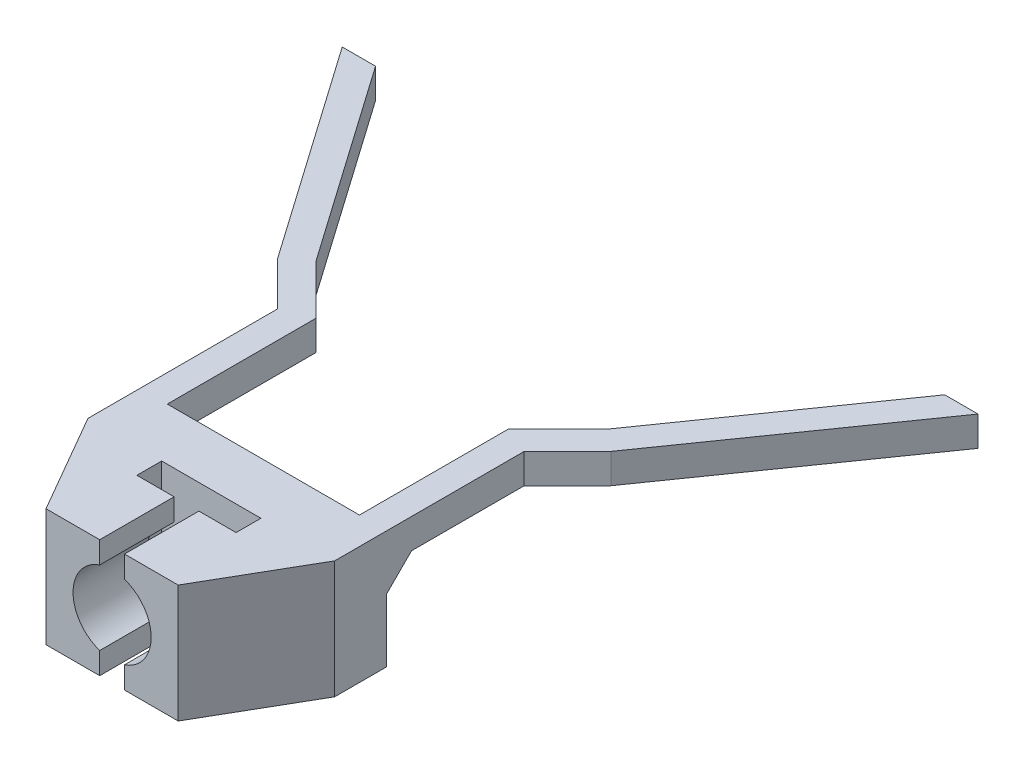
SolidWorks part; units mm, degrees
ref_plane "Front" through (0, 0, 0) normal (0, 0, 1) x (1, 0, 0)
ref_plane "Top" through (0, 0, 0) normal (0, 1, 0) x (1, 0, 0)
ref_plane "Right" through (0, 0, 0) normal (1, 0, 0) x (0, 0, -1)
ref_axis "X" through (-80.9, 0, 0) along (1, 0, 0)
ref_axis "Y" through (0, -50, 0) along (0, 1, 0)
ref_axis "Z" through (0, 0, -80.9) along (0, 0, 1)
sketch "Sketch1" plane through (0, 0, 0) normal (0, 1, 0) x (1, 0, 0)
  line L0 (-7.75, 0) -> (0, 0)
  line L1 (-7.75, 0) -> (-7.75, 12)
  line L2 (-11.75, 16) -> (-22.9533, 32)
  line L3 (-22.9533, 32) -> (-25.639, 32)
  line L4 (-7.75, 12) -> (-11.75, 16)
  line L5 (0, 0) -> (0, 35.6379) construction
  line L6 (-9.95, -2.2) -> (0, -2.2)
  line L7 (-9.95, -2.2) -> (-9.95, 11.0887)
  line L8 (-9.95, 11.0887) -> (-13.4417, 14.5805)
  line L9 (-13.4417, 14.5805) -> (-25.639, 32)
  line L10 (-13.4417, 14.5805) -> (-24.0986, 29.8) construction
  line L11 (-24.0986, 29.8) -> (-26.1692, 29.8) construction
  line L12 (-22.9533, 32) -> (-26.1692, 32) construction
  line L13 (0, 0) -> (0, -2.2)
  dimension "D1" = 15.5
  dimension "D2" = 12
  dimension "D3" = 45
  dimension "D4" = 35
  dimension "D5" = 4
  dimension "D6" = 32
  dimension "D7" = 2.2
extrude "Boss-Extrude1" add sketch "Sketch1" along normal mid plane 2.4
mirror "Mirror1" about plane through (0, 1.2, 0) normal (-1, 0, 0) of "Boss-Extrude1"
sketch "Sketch2" plane through (0, 0, 2.2) normal (0, 0, 1) x (1, 0, 0)
  line L0 (-9.95, 1.2) -> (9.95, 1.2) construction
  line L1 (-9.95, 1.2) -> (9.95, 1.2)
  line L2 (-9.95, 1.2) -> (-9.95, -8.3)
  line L3 (-9.95, -8.3) -> (9.95, -8.3)
  line L4 (9.95, 1.2) -> (9.95, -8.3)
  line L5 (-9.95, 1.2) -> (9.95, -8.3) construction
  line L6 (-9.95, -8.3) -> (9.95, 1.2) construction
  point P4 (0, -3.55)
  point P7 (0, 0)
  point P9 (0, 0)
  point P11 (0, 0)
  point P13 (0, 0)
  dimension "D1" = 9.5
extrude "Boss-Extrude2" add sketch "Sketch2" against normal up to surface (2.2 mm away) and the other way blind 10 up to face at (0, 0, 0)
sketch "Sketch3" plane through (0, 0, 12.2) normal (0, 0, 1) x (1, 0, 0)
  line L0 (0, 0) -> (0, -3.55) construction
  line L2 (-9.95, -3.55) -> (0, -3.55) construction
  line L3 (-9.95, 1.2) -> (-9.95, -8.3) construction
  line L4 (-1, -0.5629) -> (-1, 1.2)
  line L5 (9.95, 1.2) -> (-9.95, 1.2) construction
  line L6 (-1, 1.2) -> (1, 1.2)
  line L7 (1, 1.2) -> (1, -0.5629)
  line L8 (1, -6.5371) -> (1, -8.3)
  line L9 (-9.95, -8.3) -> (9.95, -8.3) construction
  line L10 (1, -8.3) -> (-1, -8.3)
  line L11 (-1, -8.3) -> (-1, -6.5371)
  arc A0 (-1, -0.5629) -> (-1, -6.5371) centre (0, -3.55) ccw
  arc A1 (1, -6.5371) -> (1, -0.5629) centre (0, -3.55) ccw
  dimension "D1" = 6.3
  dimension "D2" = 2
extrude "Cut-Extrude1" cut sketch "Sketch3" against normal blind 8
sketch "Sketch4" plane through (0, 0, 0) normal (0, 1, 0) x (1, 0, 0)
  line L0 (0, -5.2) -> (0, 0) construction
  line L1 (-4, -4.2) -> (4, -4.2)
  line L2 (-4, -4.2) -> (-4, -6.2)
  line L3 (-4, -6.2) -> (4, -6.2)
  line L4 (4, -4.2) -> (4, -6.2)
  line L5 (-4, -4.2) -> (4, -6.2) construction
  line L6 (-4, -6.2) -> (4, -4.2) construction
  line L7 (7.75, 0) -> (-7.75, 0) construction
  line L9 (1, -4.2) -> (-1, -4.2) construction
  point P4 (0, -5.2)
  dimension "D1" = 2
  dimension "D2" = 8
extrude "Cut-Extrude2" cut sketch "Sketch4" against normal through all both and the other way through all
chamfer "Chamfer1" distance 2 angle 45 2 edges at (8.85, -1.2, 0) (-8.85, -1.2, 0)
chamfer "Chamfer2" distance 8 angle 30 2 edges at (9.95, -3.55, 12.2) (-9.95, -3.55, 12.2) first distance on face at (9.95, -2.8286, 0.0318) first distance on face at (-9.95, -2.8286, 0.0318)
